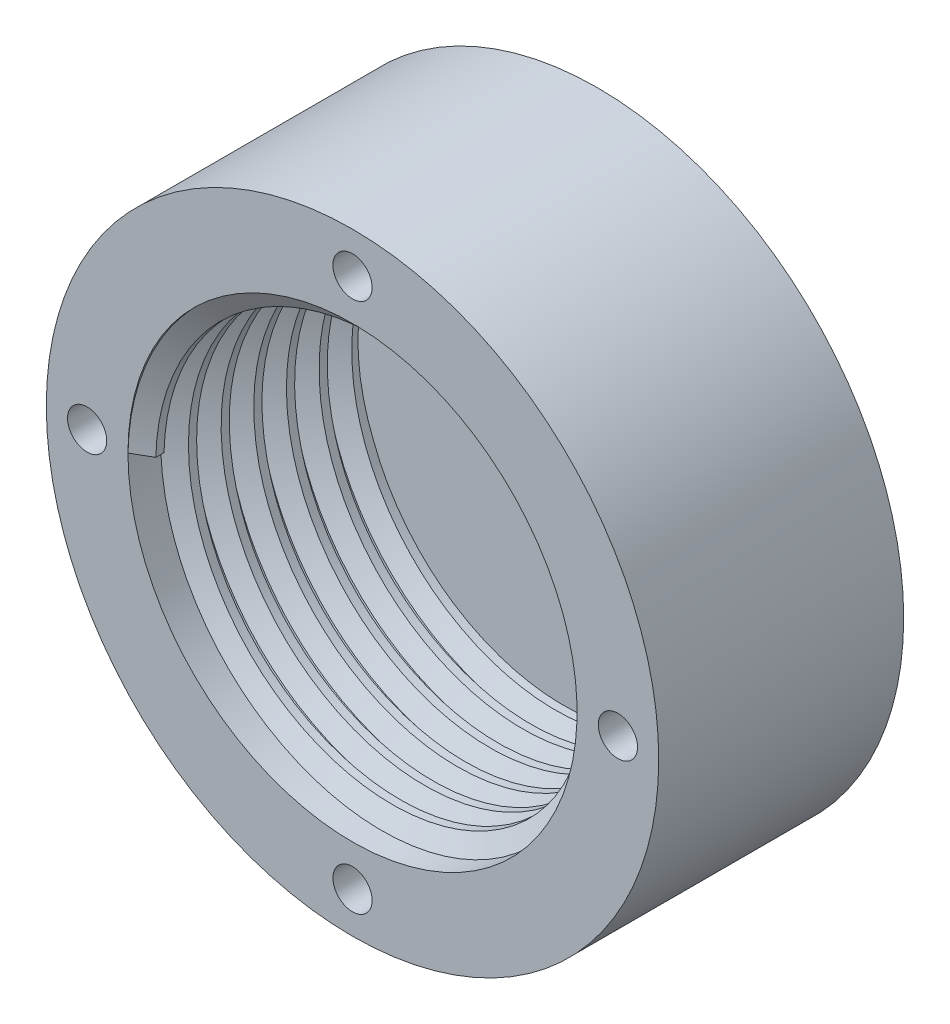
SolidWorks part; units mm, degrees
ref_plane "Alzado" through (0, 0, 0) normal (0, 0, 1) x (1, 0, 0)
ref_plane "Planta" through (0, 0, 0) normal (0, 1, 0) x (1, 0, 0)
ref_plane "Vista lateral" through (0, 0, 0) normal (1, 0, 0) x (0, 0, -1)
sketch "Croquis1" plane through (0, 0, 0) normal (0, 0, 1) x (1, 0, 0)
  circle A0 centre (0, 0) radius 37.5
  dimension "D1" = 75
extrude "Saliente-Extruir1" add sketch "Croquis1" along normal blind 30
sketch "Croquis2" plane through (0, 0, 30) normal (0, 0, 1) x (1, 0, 0)
  circle A0 centre (0, 0) radius 27.5
  dimension "D1" = 55
extrude "Cortar-Extruir1" cut sketch "Croquis2" against normal blind 26 contours A0
thread "Rosca1" pitch 4 method extrude profile "Perfil de rosca1" start angle 0, offset 0, length 25, pitch 4, diameter 55
ref_plane "Plano1" through (-27.5, 0, 30) normal (0, -1, 0) x (-1, 0, 0)
sketch "Perfil de rosca1" plane through (-27.5, 0, 30) normal (0, -1, 0) x (-1, 0, 0)
  line L0 (0, 0) -> (0, 4) construction
  line L11 (0, 0) -> (0, 3.5)
  line L12 (0, 3.5) -> (-2.1651, 2.25)
  line L13 (-2.1651, 2.25) -> (-2.1651, 1.25)
  line L15 (-2.1651, 1.25) -> (0, 0)
  line L17 (-2.1651, 1.75) -> (0, 1.75) construction
  point P2 (0, 0)
  dimension "Pitch" = 4
  dimension "Profile_Angle" = 60
  dimension "Profile_Land" = 1
  dimension "Profile_Height" = 2.1651
sketch "Croquis10" plane through (0, 0, 0) normal (0, 0, -1) x (-1, 0, 0)
  circle A0 centre (0, 0) radius 6.55
  dimension "D1" = 13.1
extrude "Cortar-Extruir2" cut sketch "Croquis10" against normal blind 10
sketch "Croquis12" plane through (0, 0, 30) normal (0, 0, 1) x (1, 0, 0)
  line L0 (0, 37.5) -> (0, 32.5) construction
  line L1 (0, 0) -> (-12.3026, 0) construction
  line L2 (37.5, 0) -> (32.5, 0) construction
  circle A0 centre (0, 0) radius 37.5 construction
  circle A6 centre (0, 32.5) radius 2.4
  circle A7 centre (32.5, 0) radius 2.4
  circle A8 centre (0, -32.5) radius 2.4
  circle A9 centre (-32.5, 0) radius 2.4
  dimension "D2" = 4.8
  dimension "D4" = 5
  dimension "D1" = 5
  dimension "D3" = 4
extrude "Cortar-Extruir3" cut sketch "Croquis12" against normal blind 34
